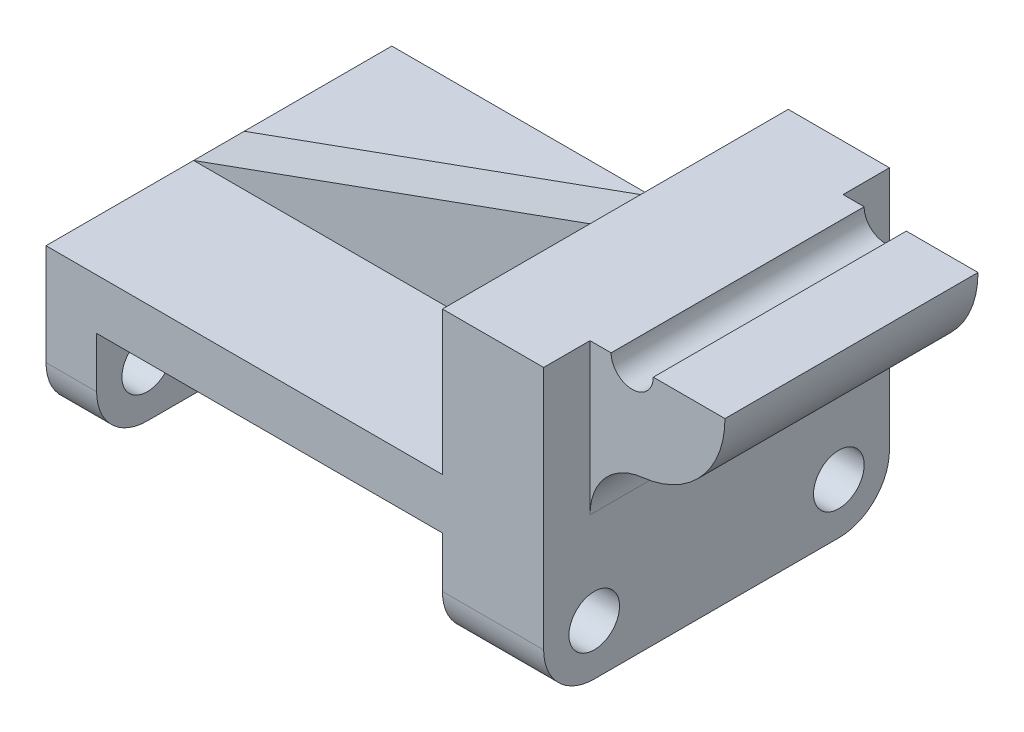
SolidWorks part; units mm, degrees
ref_plane "Front Plane" through (0, 0, 0) normal (0, 0, 1) x (1, 0, 0)
ref_plane "Top Plane" through (0, 0, 0) normal (0, 1, 0) x (1, 0, 0)
ref_plane "Right Plane" through (0, 0, 0) normal (1, 0, 0) x (0, 0, -1)
sketch "Sketch1" plane through (0, 0, 0) normal (0, 0, 1) x (1, 0, 0)
  line L0 (0, 0) -> (0, 36)
  line L1 (0, 36) -> (94, 36)
  line L2 (94, 36) -> (94, 70)
  line L3 (94, 70) -> (118, 70)
  line L4 (118, 70) -> (118, 0)
  line L5 (118, 0) -> (94, 0)
  line L6 (94, 0) -> (94, 24)
  line L7 (94, 24) -> (12, 24)
  line L8 (12, 24) -> (12, 0)
  line L9 (12, 0) -> (0, 0)
  dimension "D1" = 70
  dimension "D2" = 82
  dimension "D3" = 106
  dimension "D4" = 36
  dimension "D5" = 12
  dimension "D6" = 12
extrude "Boss-Extrude1" add sketch "Sketch1" along normal blind 41 and the other way blind 41
fillet "Fillet1" radius 12 4 edges at (106, 0, -41) (106, 0, 41) (6, 0, 41) (6, 0, -41)
hole_wizard "Ø12.0mm Dowel Hole1" positions "Sketch6" profile "Sketch5" hole size "Ø12.0" standard "ISO" end condition through all
sketch "Sketch6" plane through (0, 0, 0) normal (-1, 0, 0) x (0, 0, 1)
  point P0 (-29, 12)
  point P3 (29, 12)
sketch "Sketch5" plane through (0, 12, -29) normal (0, 1, 0) x (0, 0, 1)
  line L0 (0, 0) -> (0, 118)
  line L1 (0, 118) -> (6, 118)
  line L2 (6, 118) -> (6, 0.025)
  line L3 (6, 0.025) -> (6.025, 0)
  line L5 (6.025, 0) -> (0, 0)
  line L6 (-6, 0.025) -> (-6.025, 0) construction
  line L11 (0, -6.35) -> (0, 107.95) construction
  dimension "Thru Hole Dia." = 12
  dimension "Thru Hole Depth" = 118
  dimension "Near C'Sink Dia." = 12.05
  dimension "Near C'Sink Angle" = 90
sketch "Sketch7" plane through (0, 0, 0) normal (0, 0, 1) x (1, 0, 0)
  line L0 (118, 12) -> (118, 70) construction
  line L2 (118, 34.2229) -> (118, 70)
  line L4 (118, 70) -> (128, 70)
  line L6 (128, 70) -> (150, 70)
  line L7 (118, 70) -> (128, 70)
  arc A1 (130.4444, 48.1362) -> (118, 34.2229) centre (132, 34.2229) ccw
  arc A2 (130.4444, 48.1362) -> (150, 70) centre (128, 70) ccw
  dimension "D1" = 22
  dimension "D2" = 28
  dimension "D3" = 10
extrude "Boss-Extrude2" add sketch "Sketch7" along normal blind 30 and the other way blind 30 contours L4 L6 A2 A1 L2
sketch "Sketch8" plane through (0, 0, 30) normal (0, 0, 1) x (1, 0, 0)
  circle A0 centre (128, 70) radius 5
  dimension "D1" = 10
extrude "Cut-Extrude1" cut sketch "Sketch8" against normal through all
sketch "Sketch9" plane through (0, 0, 0) normal (0, 0, 1) x (1, 0, 0)
  line L0 (0, 36) -> (94, 70)
  line L1 (94, 70) -> (94, 36)
  line L2 (94, 36) -> (0, 36)
extrude "Boss-Extrude3" add sketch "Sketch9" along normal blind 6 and the other way blind 6
